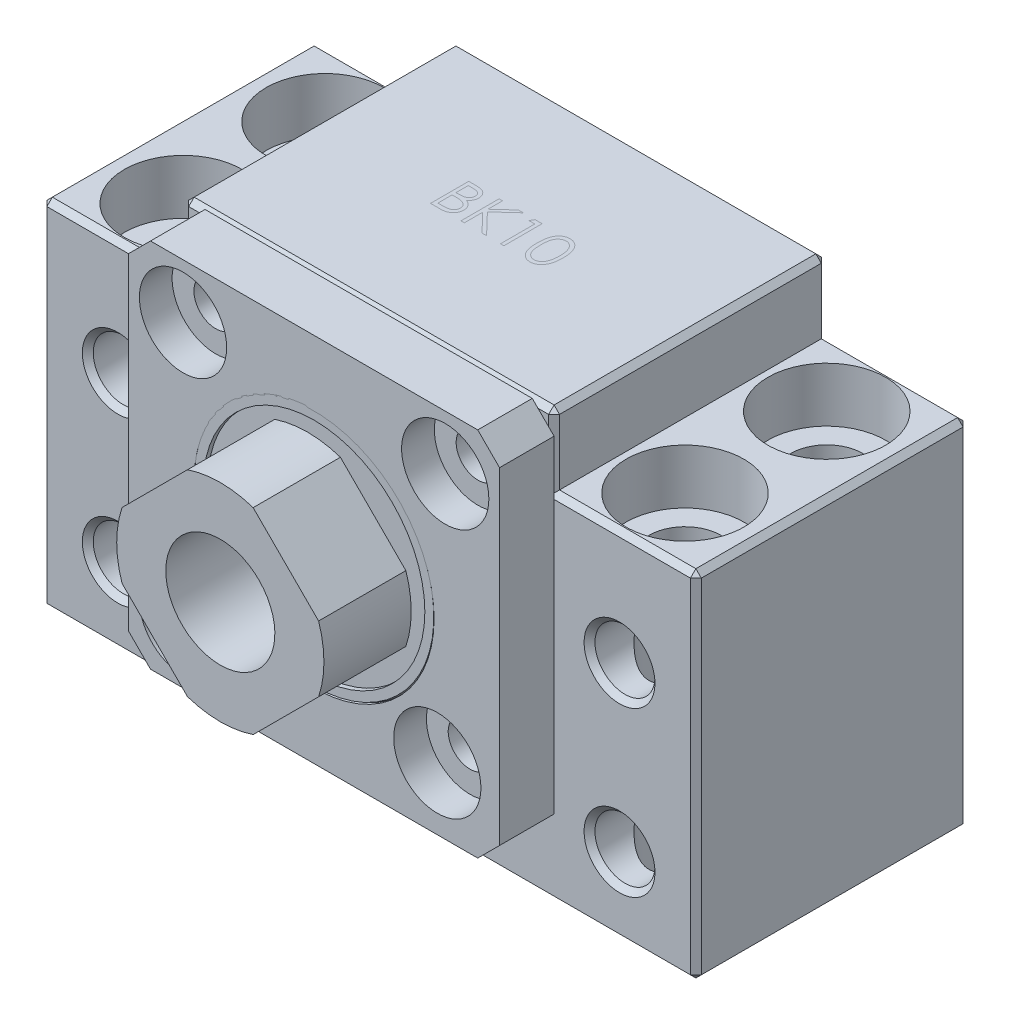
SolidWorks part; units mm, degrees
material "1060 Alloy"
ref_plane "Front Plane" through (0, 0, 0) normal (0, 0, 1) x (1, 0, 0)
ref_plane "Top Plane" through (0, 0, 0) normal (0, 1, 0) x (1, 0, 0)
ref_plane "Right Plane" through (0, 0, 0) normal (1, 0, 0) x (0, 0, -1)
ref_plane "Plane1" through (0, 0, -10) normal (0, 0, -1) x (-1, 0, 0)
sketch "Sketch1" plane through (0, 0, -10) normal (0, 0, -1) x (-1, 0, 0)
  line L0 (30, -0.1215) -> (30, 38.8785) construction
  line L1 (30, 38.8785) -> (-30, 38.8785) construction
  line L2 (-30, 38.8785) -> (-30, -0.1215) construction
  line L3 (-30, -0.1215) -> (30, -0.1215)
  line L4 (30, 32.3785) -> (-30, 32.3785) construction
  line L5 (0, 38.8785) -> (0, 0) construction
  line L6 (-17, 38.8785) -> (-17, 32.3785)
  line L7 (17, 38.8785) -> (17, 32.3785)
  line L8 (30, -0.1215) -> (30, 32.3785)
  line L9 (-30, 32.3785) -> (-30, -0.1215)
  line L10 (-17, 38.8785) -> (17, 38.8785)
  line L11 (30, 32.3785) -> (17, 32.3785)
  line L12 (-30, 32.3785) -> (-17, 32.3785)
  line L13 (17, 38.8785) -> (17, 0) construction
  line L14 (-17, 38.8785) -> (-17, 0) construction
  line L16 (23, 6.8985) -> (-23, 6.8985) construction
  line L17 (23, 6.8985) -> (23, 21.8985) construction
  line L18 (23, 21.8985) -> (-23, 21.8985) construction
  line L19 (-23, 6.8985) -> (-23, 21.8985) construction
  line L20 (23, 6.8985) -> (-23, 21.8985) construction
  line L21 (23, 21.8985) -> (-23, 6.8985) construction
  circle A0 centre (-23, 21.8985) radius 2.75
  circle A1 centre (23, 21.8985) radius 2.75
  circle A2 centre (23, 6.8985) radius 2.75
  circle A3 centre (-23, 6.8985) radius 2.75
  point P4 (-30, 19.3785)
  point P14 (0, 14.3985)
  dimension "D9" = 5.5
  dimension "D10" = 5.5
  dimension "D11" = 5.5
  dimension "D12" = 5.5
  dimension "D1" = 60
  dimension "D2" = 39
  dimension "D3" = 32.5
  dimension "D6" = 15
  dimension "D7" = 22.02
  dimension "D8" = 46
  dimension "D4" = 17
  dimension "D5" = 17
extrude "Boss-Extrude1" add sketch "Sketch1" against normal blind 25
hole_wizard "Hole1" positions "Sketch5" profile "Sketch4" legacy
sketch "Sketch5" plane through (0, 0, 15) normal (0, 0, -1) x (-1, 0, 0)
  line L0 (30, -0.1215) -> (30, 32.3785) construction
  line L1 (-30, -0.1215) -> (30, -0.1215) construction
  point P0 (0, 21.8985)
  dimension "D1" = 30
  dimension "D2" = 22.02
sketch "Sketch4" plane through (0, 21.8985, 15) normal (1, 0, 0) x (0, -1, 0)
  line L0 (0, 0) -> (0, 25)
  line L1 (0, 25) -> (10.5, 25)
  line L2 (10.5, 25) -> (10.5, 20)
  line L3 (10.5, 20) -> (13, 20)
  line L4 (13, 20) -> (13, 0)
  line L5 (13, 0) -> (0, 0)
  line L6 (0, 110) -> (0, -10) construction
  dimension "Diameter" = 21
  dimension "C-Bore Diameter" = 26
  dimension "C-Bore Depth" = 20
sketch "Sketch10" plane through (0, 32.3785, 0) normal (0, 1, 0) x (1, 0, 0)
  line L0 (-30, 4) -> (30, 4) construction
  line L3 (0, 10) -> (0, -15) construction
  line L4 (-17, 10) -> (17, 10) construction
  line L5 (-17, -15) -> (17, -15) construction
  line L7 (17, 10) -> (30, 10) construction
  line L8 (-30, -9) -> (30, -9) construction
  line L9 (-30, -15) -> (-30, 10) construction
  line L10 (30, -15) -> (30, 10) construction
  circle A0 centre (-23, 4) radius 3.3
  circle A1 centre (23, 4) radius 3.3
  circle A2 centre (-23, -9) radius 3.3
  circle A3 centre (23, -9) radius 3.3
  dimension "D1" = 6.6
  dimension "D2" = 6.6
  dimension "D3" = 46
  dimension "D4" = 23
  dimension "D7" = 6.6
  dimension "D8" = 6.6
  dimension "D5" = 6
  dimension "D6" = 13
extrude "Cut-Extrude3" cut sketch "Sketch10" against normal through all
sketch "Sketch11" plane through (0, 32.3785, 0) normal (0, 1, 0) x (1, 0, 0)
  circle A0 centre (-23, 4) radius 5.4
  circle A1 centre (23, 4) radius 5.4
  circle A2 centre (-23, -9) radius 5.4
  circle A3 centre (23, -9) radius 5.4
  dimension "D1" = 10.8
  dimension "D2" = 10.8
  dimension "D3" = 10.8
  dimension "D4" = 10.8
extrude "Cut-Extrude4" cut sketch "Sketch11" against normal blind 5
chamfer "Chamfer3" distance 0.5 angle 45 32 edges at (0, -0.1215, -10) (30, 16.1285, -10) (23.5, 32.3785, -10) (17, 35.6285, -10) (0, 38.8785, -10) (-17, 35.6285, -10) (-23.5, 32.3785, -10) (-30, 16.1285, -10) (20.25, 21.8985, -10) (-25.75, 21.8985, -10) (-25.75, 6.8985, -10) (20.25, 6.8985, -10) (-23.5, 32.3785, 15) (-17, 35.6285, 15) (0, 38.8785, 15) (17, 35.6285, 15) (23.5, 32.3785, 15) (30, 16.1285, 15) (0, -0.1215, 15) (-30, 16.1285, 15) (20.25, 21.8985, 15) (-25.75, 21.8985, 15) (-25.75, 6.8985, 15) (20.25, 6.8985, 15) (-30, 32.3785, 2.5) (-30, -0.1215, 2.5) (30, -0.1215, 2.5) (30, 32.3785, 2.5) (17, 38.8785, 2.5) (-17, 38.8785, 2.5) (13, 21.8985, 15) (10.5, 21.8985, -10)
sketch "Sketch14" plane through (0, 0, 15) normal (0, 0, 1) x (1, 0, 0)
  line L0 (-15, 38.8985) -> (-17, 36.8985)
  line L1 (15, 4.8985) -> (-15, 4.8985)
  line L2 (17, 6.8985) -> (17, 36.8985)
  line L3 (15, 38.8985) -> (-15, 38.8985)
  line L4 (-17, 6.8985) -> (-17, 36.8985)
  line L5 (17, 4.8985) -> (-17, 38.8985) construction
  line L6 (17, 38.8985) -> (-17, 4.8985) construction
  line L7 (17, 36.8985) -> (15, 38.8985)
  line L8 (15, 4.8985) -> (17, 6.8985)
  line L9 (-15, 4.8985) -> (-17, 6.8985)
  circle A0 centre (0, 21.8985) radius 17 construction
  circle A1 centre (-12.0208, 9.8777) radius 2
  circle A2 centre (11.293, 10.6055) radius 2
  circle A3 centre (12.0208, 33.9193) radius 2
  circle A4 centre (-12.0208, 33.9193) radius 2
  circle A5 centre (0, 21.8985) radius 11
  point P0 (0, 21.8985)
  dimension "D3" = 4
  dimension "D4" = 4
  dimension "D5" = 4
  dimension "D6" = 4
  dimension "D11" = 22
  dimension "D1" = 34
  dimension "D2" = 34
  dimension "D12" = 17
extrude "Boss-Extrude2" add sketch "Sketch14" along normal blind 5 separate body
sketch "Sketch15" plane through (0, 0, 20) normal (0, 0, 1) x (1, 0, 0)
  circle A0 centre (-12.0208, 33.9193) radius 4
  circle A1 centre (12.0208, 33.9193) radius 4
  circle A2 centre (-12.0208, 9.8777) radius 4
  circle A3 centre (11.293, 10.6055) radius 4
  dimension "D1" = 8
  dimension "D2" = 8
  dimension "D3" = 8
  dimension "D4" = 8
extrude "Cut-Extrude5" cut sketch "Sketch15" against normal blind 3
sketch "Sketch16" plane through (0, 0, 0) normal (1, 0, 0) x (0, 0, -1)
  line L0 (-15, 22.02) -> (9.0178, 22.02) construction
  line L1 (-19.5729, 15.02) -> (-20.6, 15.02)
  line L2 (-20.6, 15.02) -> (-20.6, 12.52)
  line L3 (5, 17.02) -> (10.4, 17.02)
  line L4 (5, 32.3985) -> (5, 11.3985) construction
  line L5 (10.4, 17.02) -> (10.4, 15.016)
  line L6 (10.4, 15.016) -> (8.3452, 15.016)
  line L7 (8.3452, 15.016) -> (8.3452, 13.0747)
  line L8 (8.3452, 13.0747) -> (9.5052, 13.0747)
  line L9 (9.5052, 13.0747) -> (9.5052, 11.4736)
  line L10 (9.5052, 11.4736) -> (5, 11.4736)
  line L11 (5, 11.4736) -> (5, 13.0747)
  line L12 (5, 13.0747) -> (6.0458, 13.0747)
  line L13 (6.0458, 13.0747) -> (6.0458, 15.02)
  line L14 (6.0458, 15.02) -> (5, 15.02)
  line L15 (5, 34.8985) -> (5, 8.8985) construction
  line L16 (5, 15.02) -> (5, 17.02)
  line L17 (10, 31.8785) -> (10, 0.3785) construction
  line L18 (5, 17.02) -> (5, 8.8985)
  line L19 (5, 8.8985) -> (-11, 8.8985)
  line L20 (-11, 8.8985) -> (-11, 17.02)
  line L21 (-11, 17.02) -> (5, 17.02)
  line L22 (-19.5729, 15.02) -> (-19.5729, 11.8671)
  line L23 (-19.5729, 11.8671) -> (-20, 11.8671)
  line L24 (-20, 36.8985) -> (-20, 6.8985) construction
  line L25 (-20.6, 17.02) -> (-20.6, 16.6237)
  line L26 (-16.6, 15.016) -> (-14.4452, 15.016)
  line L27 (-14.4452, 15.016) -> (-14.4452, 13.0747)
  line L28 (-14.4452, 13.0747) -> (-15.538, 13.0747)
  line L29 (-15.538, 13.0747) -> (-15.538, 10.9304)
  line L30 (-15.538, 10.9304) -> (-11.1266, 10.9304)
  line L31 (-11.1266, 10.9304) -> (-11.1266, 13.0746)
  line L32 (-11.1266, 13.0746) -> (-12.2547, 13.0746)
  line L33 (-12.2547, 13.0746) -> (-12.2547, 15.0199)
  line L34 (-12.2547, 15.0199) -> (-11.1373, 15.0199)
  line L35 (-11.1373, 15.0199) -> (-11.1373, 17.02)
  line L36 (-11.1373, 17.02) -> (-16.6, 17.02)
  line L37 (-16.6, 17.02) -> (-16.6, 15.016)
  line L38 (-20.6, 16.6237) -> (-16.7129, 16.6237)
  line L40 (-16.7129, 16.6237) -> (-16.7129, 15.02)
  line L41 (-20.6, 12.52) -> (-28.6, 12.52)
  line L42 (-28.6, 12.52) -> (-28.6, 17.02)
  line L43 (-28.6, 17.02) -> (-20.6, 17.02)
  line L44 (-20, 11.8671) -> (-20, 11.0464)
  line L45 (-20, 11.0464) -> (-19.7865, 10.9304)
  line L46 (-19.7865, 10.9304) -> (-16.7129, 10.9304)
  line L47 (-16.7129, 10.9304) -> (-16.7129, 15.02)
  point P7 (5.5229, 15.02)
  dimension "D1" = 22.02
  dimension "D2" = 5
  dimension "D3" = 2
  dimension "D4" = 0.4
  dimension "D5" = 10.5464
  dimension "D6" = 16
  dimension "D7" = 27
  dimension "D8" = 31
  dimension "D9" = 9.5
  dimension "D10" = 8
  dimension "D11" = 7
revolve "Revolve1" add sketch "Sketch16" angle 360 about L0 region at (0, 14.4803, 22.4931) region at (0, 14.4262, -7.4568) region at (0, 12.9593, 3) region at (0, 14.1373, 13.5738)
sketch "Sketch17" plane through (0, 0, 28.6) normal (0, 0, 1) x (1, 0, 0)
  line L0 (0, 31.52) -> (0, 12.52) construction
  line L1 (0, 12.52) -> (9.5, 22.02) construction
  line L2 (9.5, 22.02) -> (0, 31.52) construction
  line L3 (0, 31.52) -> (-9.5, 22.02) construction
  line L4 (-9.5, 22.02) -> (0, 12.52) construction
  line L5 (-1.9946, 32.0462) -> (-10.0681, 23.9727)
  line L6 (-10.1121, 20.1112) -> (-1.9946, 11.9938)
  line L7 (1.9946, 11.9938) -> (10.0681, 20.0673)
  line L8 (10.0681, 23.9727) -> (1.9946, 32.0462)
  line L9 (0, 34.0408) -> (-12.0208, 22.02) construction
  line L10 (-12.0208, 22.02) -> (0, 9.9992) construction
  line L11 (0, 9.9992) -> (12.0208, 22.02) construction
  line L12 (12.0208, 22.02) -> (0, 34.0408) construction
  line L13 (-1.9946, 32.0462) -> (1.9946, 32.0462)
  line L14 (-10.0681, 23.9727) -> (-10.1121, 20.1112)
  line L15 (-1.9946, 11.9938) -> (1.9946, 11.9938)
  line L16 (10.0681, 23.9727) -> (10.0681, 20.0673)
  circle A0 centre (0, 22.02) radius 9.5 construction
  circle A1 centre (0, 22.02) radius 11
  dimension "D3" = 22
  dimension "D1" = 13.435
  dimension "D2" = 1.7825
extrude "Cut-Extrude6" cut sketch "Sketch17" against normal blind 8
sketch "Sketch18" plane through (0, 38.8785, 0) normal (0, 1, 0) x (1, 0, 0)
  text T0 "BK10"
wrap "Wrap1" sketch "Sketch18" wrap type scribe source sketch "Sketch18" face at (0, 38.8785, 2.5)
